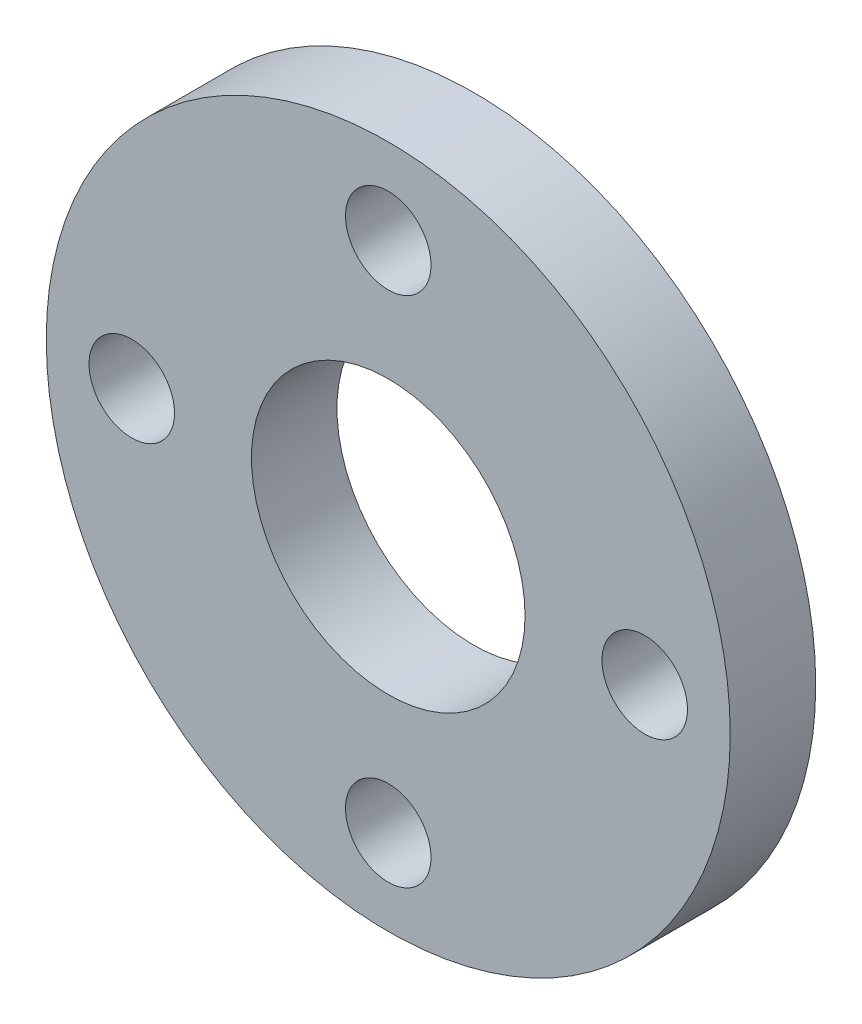
SolidWorks part; units mm, degrees
material "Pine"
ref_plane "Front Plane" through (0, 0, 0) normal (0, 0, 1) x (1, 0, 0)
ref_plane "Top Plane" through (0, 0, 0) normal (0, 1, 0) x (1, 0, 0)
ref_plane "Right Plane" through (0, 0, 0) normal (1, 0, 0) x (0, 0, -1)
sketch "Sketch1" plane through (0, 0, 0) normal (0, 0, 1) x (1, 0, 0)
  circle A0 centre (0, 228.6) radius 10.16
  circle A1 centre (0, 228.6) radius 25.4
  circle A3 centre (0, 247.65) radius 3.175
  circle A4 centre (19.05, 228.6) radius 3.175
  circle A5 centre (0, 209.55) radius 3.175
  circle A6 centre (-19.05, 228.6) radius 3.175
  circle A7 centre (0, 228.6) radius 12.7 construction
  point P18 (0, 228.6)
  dimension "D1" = 19.05
  dimension "D2" = 50.8
  dimension "D3" = 6.35
  dimension "D5" = 20.32
  dimension "D4" = 4
extrude "Boss-Extrude1" add sketch "Sketch1" along normal blind 6.35
